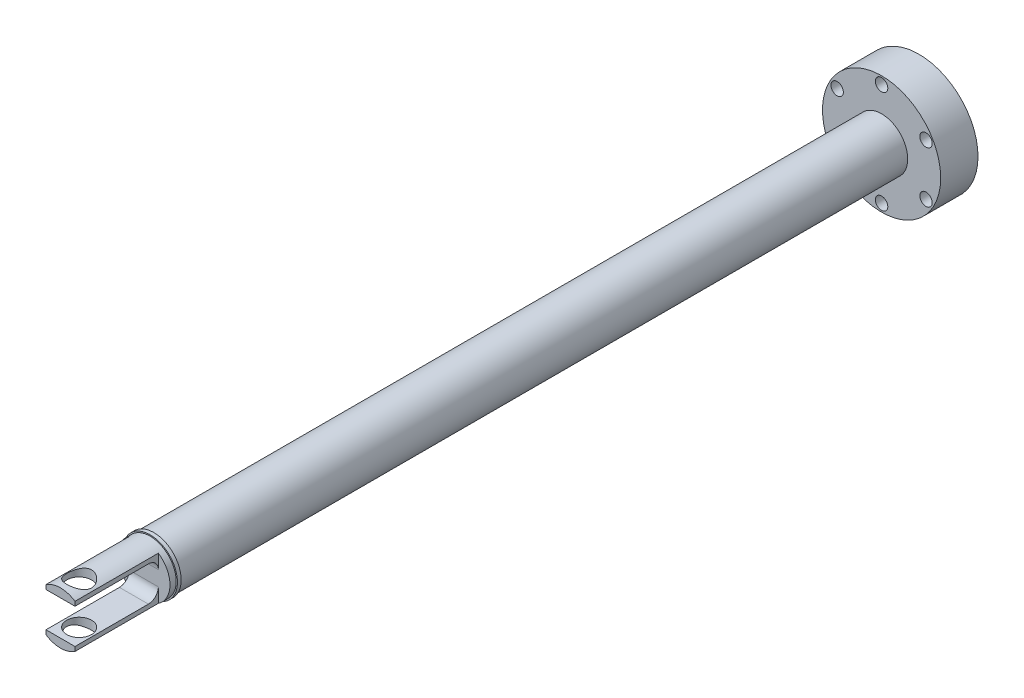
SolidWorks part; units mm, degrees
ref_plane "Płaszczyzna przednia" through (0, 0, 0) normal (0, 0, 1) x (1, 0, 0)
ref_plane "Płaszczyzna górna" through (0, 0, 0) normal (0, 1, 0) x (1, 0, 0)
ref_plane "Płaszczyzna prawa" through (0, 0, 0) normal (1, 0, 0) x (0, 0, -1)
sketch "Szkic1" plane through (0, 0, 0) normal (0, 0, 1) x (1, 0, 0)
  circle A0 centre (0, 0) radius 47.5
  dimension "D1" = 95
extrude "Dodanie-wyciągnięcie1" add sketch "Szkic1" along normal blind 30 contours A0
sketch "Szkic2" plane through (0, 0, 30) normal (0, 0, 1) x (1, 0, 0)
  circle A0 centre (0, 41.25) radius 5
  dimension "D1" = 10
  dimension "D2" = 41.25
extrude "Wytnij-wyciągnięcie1" cut sketch "Szkic2" against normal up to next
pattern_circular "Szyk kołowy1" count 6 over 360 about axis through (0, 0, 30) along (0, 0, 1) of "Wytnij-wyciągnięcie1"
sketch "Szkic3" plane through (0, 0, 30) normal (0, 0, 1) x (1, 0, 0)
  circle A0 centre (0, 0) radius 21
  dimension "D1" = 42
extrude "Dodanie-wyciągnięcie2" add sketch "Szkic3" along normal blind 585
sketch "Szkic4" plane through (0, 0, 615) normal (0, 0, 1) x (1, 0, 0)
  line L0 (-15.6525, 14) -> (15.6525, 14)
  line L1 (-15.6525, -14) -> (15.6525, -14)
  circle A1 centre (0, 0) radius 21 construction
  arc A2 (-15.6525, -14) -> (15.6525, -14) centre (0, 0) ccw
  arc A3 (15.6525, 14) -> (-15.6525, 14) centre (0, 0) ccw
  dimension "D1" = 14
  dimension "D2" = 14
extrude "Dodanie-wyciągnięcie3" add sketch "Szkic4" along normal blind 75
sketch "Szkic5" plane through (0, 0, 615) normal (0, 0, 1) x (1, 0, 0)
  circle A0 centre (0, 0) radius 22
  dimension "D1" = 44
extrude "Dodanie-wyciągnięcie4" add sketch "Szkic5" along normal blind 3
sketch "Szkic7" plane through (0, 0, 618) normal (0, 0, 1) x (1, 0, 0)
  circle A0 centre (0, 0) radius 21 construction
  circle A1 centre (0, 0) radius 21
extrude "Dodanie-wyciągnięcie5" add sketch "Szkic7" along normal blind 5
sketch "Szkic8" plane through (0, -14, 0) normal (0, 1, 0) x (1, 0, 0)
  line L0 (-15.6525, -690) -> (15.6525, -690) construction
  line L2 (15.6525, -690) -> (-15.6525, -690) construction
  circle A0 centre (0, -675) radius 10
  point P6 (0, -690)
  dimension "D1" = 20
  dimension "D2" = 15
extrude "Wytnij-wyciągnięcie2" cut sketch "Szkic8" against normal up to next and the other way through all
sketch "Szkic9" plane through (0, 0, 690) normal (0, 0, 1) x (1, 0, 0)
  line L0 (-11.6525, 14) -> (-11.6525, 17.4705)
  line L1 (-15.6525, 14) -> (15.6525, 14)
  line L2 (-15.6525, 14) -> (-11.6525, 14)
  line L3 (0, 16.8801) -> (0, 8.9496) construction
  line L4 (15.6525, 14) -> (11.6525, 14)
  line L5 (11.6525, 14) -> (11.6525, 17.4705)
  line L6 (0, 0) -> (11.8793, 0) construction
  line L7 (11.6525, -14) -> (11.6525, -17.4705)
  line L8 (15.6525, -14) -> (11.6525, -14)
  line L9 (-15.6525, -14) -> (-11.6525, -14)
  line L10 (-11.6525, -14) -> (-11.6525, -17.4705)
  arc A0 (11.6525, 17.4705) -> (15.6525, 14) centre (0, 0) cw
  arc A1 (15.6525, 14) -> (-15.6525, 14) centre (0, 0) ccw
  arc A2 (-11.6525, 17.4705) -> (-15.6525, 14) centre (0, 0) ccw
  arc A3 (11.6525, -17.4705) -> (15.6525, -14) centre (0, 0) ccw
  arc A4 (-11.6525, -17.4705) -> (-15.6525, -14) centre (0, 0) cw
  dimension "D2" = 4
  dimension "D1" = 0
extrude "Wytnij-wyciągnięcie3" cut sketch "Szkic9" against normal up to surface (67 mm away) up to face at (0, 0, 623)
fillet "Zaokrąglenie1" radius 8 2 edges at (0, -14, 623) (0, 14, 623)
